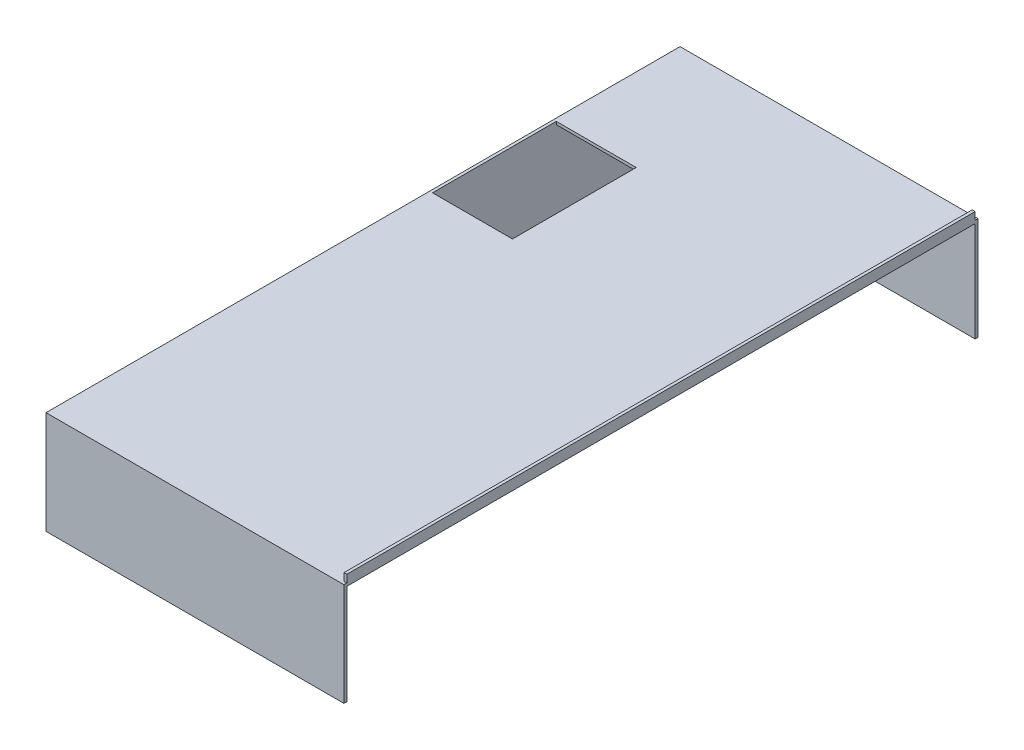
SolidWorks part; units mm, degrees
ref_plane "Front Plane" through (0, 0, 0) normal (0, 0, 1) x (1, 0, 0)
ref_plane "Top Plane" through (0, 0, 0) normal (0, 1, 0) x (1, 0, 0)
ref_plane "Right Plane" through (0, 0, 0) normal (1, 0, 0) x (0, 0, -1)
sketch "Sketch4" plane through (0, 0, 0) normal (0, 1, 0) x (1, 0, 0)
  line L0 (179.4784, 330) -> (334.4784, 330)
  line L1 (334.4784, 330) -> (334.4784, 0)
  line L2 (334.4784, 0) -> (179.4784, 0)
  line L3 (179.4784, 0) -> (179.4784, 200)
  line L4 (179.4784, 200) -> (221.4784, 200)
  line L5 (221.4784, 200) -> (221.4784, 265)
  line L6 (221.4784, 265) -> (179.4784, 265)
  line L7 (179.4784, 265) -> (179.4784, 330)
  dimension "D1" = 65
  dimension "D2" = 65
  dimension "D3" = 42
  dimension "D4" = 200
  dimension "D5" = 155
  dimension "D6" = 155
extrude "Boss-Extrude4" add sketch "Sketch4" along normal blind 1.5 separate body
sketch "Sketch5" plane through (0, 0, 0) normal (0, 0, 1) x (1, 0, 0)
  line L1 (179.4784, 1.5) -> (334.4784, 1.5)
  line L2 (179.4784, 1.5) -> (179.4784, -52.5)
  line L3 (179.4784, -52.5) -> (334.4784, -52.5)
  line L4 (334.4784, 1.5) -> (334.4784, -52.5)
  dimension "D1" = 54
sketch "Sketch7" plane through (0, 0, -330) normal (0, 0, -1) x (-1, 0, 0)
  line L1 (-179.4784, 1.5) -> (-334.4784, 1.5)
  line L2 (-179.4784, 1.5) -> (-179.4784, -52.5)
  line L3 (-179.4784, -52.5) -> (-334.4784, -52.5)
  line L4 (-334.4784, 1.5) -> (-334.4784, -52.5)
  dimension "D1" = 54
  dimension "D2" = 155
sketch "Sketch8" plane through (0, 1.5, 0) normal (0, 1, 0) x (1, 0, 0)
  line L0 (179.4784, 330) -> (334.4784, 330) construction
  line L1 (334.4784, 0) -> (332.9784, 0)
  line L2 (334.4784, 0) -> (334.4784, 330)
  line L3 (334.4784, 330) -> (332.9784, 330)
  line L4 (332.9784, 0) -> (332.9784, 330)
  dimension "D1" = 1.5
extrude "Boss-Extrude5" add sketch "Sketch5" along normal blind 1.5
extrude "Boss-Extrude14" add sketch "Sketch8" along normal blind 4
extrude "Boss-Extrude18" add sketch "Sketch7" along normal blind 1.5
sketch "Sketch9" plane through (179.4784, 0, 0) normal (-1, 0, 0) x (0, 0, 1)
  line L1 (-331.5, 1.5) -> (1.5, 1.5)
  line L2 (-331.5, 1.5) -> (-331.5, -52.5)
  line L3 (-331.5, -52.5) -> (1.5, -52.5)
  line L4 (1.5, 1.5) -> (1.5, -52.5)
extrude "Boss-Extrude19" add sketch "Sketch9" along normal blind 1.5
